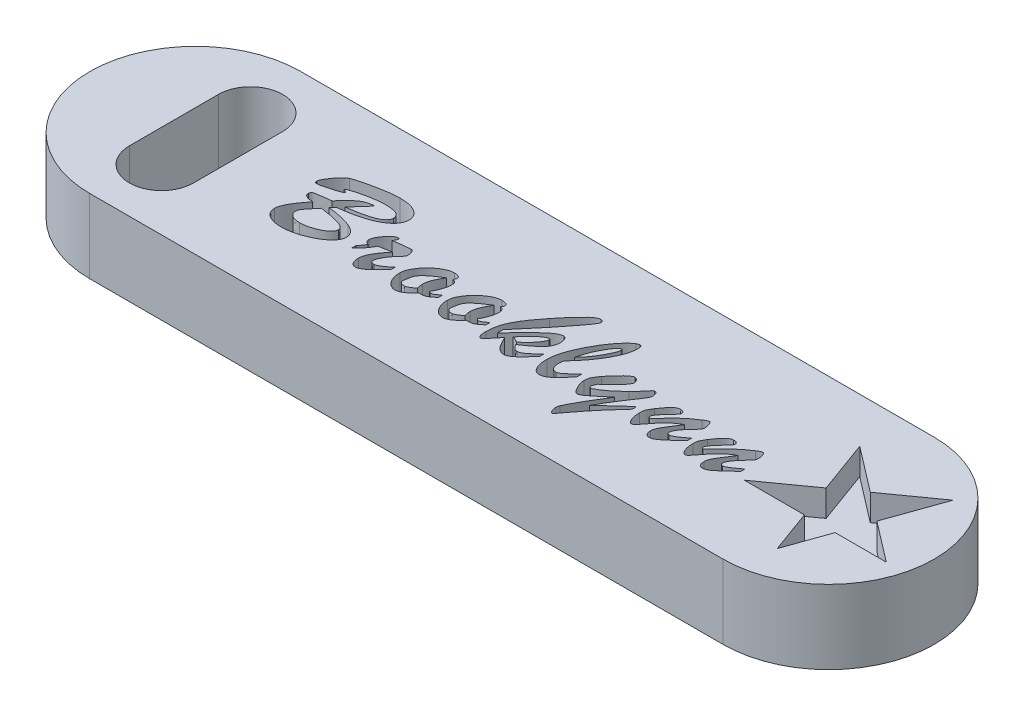
SolidWorks part; units mm, degrees
ref_plane "Front Plane" through (0, 0, 0) normal (0, 0, 1) x (1, 0, 0)
ref_plane "Top Plane" through (0, 0, 0) normal (0, 1, 0) x (1, 0, 0)
ref_plane "Right Plane" through (0, 0, 0) normal (1, 0, 0) x (0, 0, -1)
sketch "Sketch2" plane through (0, 0, 0) normal (0, 1, 0) x (1, 0, 0)
  line L0 (-42.129, 2.7124) -> (34.071, 2.7124) construction
  line L1 (-42.129, 15.4124) -> (34.071, 15.4124)
  line L2 (-42.129, -9.9876) -> (34.071, -9.9876)
  arc A0 (-42.129, 15.4124) -> (-42.129, -9.9876) centre (-42.129, 2.7124) ccw
  arc A1 (34.071, -9.9876) -> (34.071, 15.4124) centre (34.071, 2.7124) ccw
  point P2 (-4.029, 2.7124)
  dimension "D2" = 76.2
  dimension "D1" = 25.4
extrude "Boss-Extrude1" add sketch "Sketch2" along normal blind 8.89
sketch "Sketch5" plane through (0, 8.89, 0) normal (0, 1, 0) x (1, 0, 0)
  line L0 (-40.8401, 8.0714) -> (-40.8401, -2.6467) construction
  line L1 (-36.9745, 8.0714) -> (-36.9745, -2.6467)
  line L2 (-44.7056, 8.0714) -> (-44.7056, -2.6467)
  line L3 (34.071, 15.4124) -> (-42.129, 15.4124) construction
  arc A0 (-36.9745, 8.0714) -> (-44.7056, 8.0714) centre (-40.8401, 8.0714) ccw
  arc A1 (-44.7056, -2.6467) -> (-36.9745, -2.6467) centre (-40.8401, -2.6467) ccw
  point P2 (-40.8401, 2.7124)
  dimension "D1" = 12.7
extrude "Cut-Extrude1" cut sketch "Sketch5" against normal blind 38.1
sketch "Sketch6" plane through (0, 8.89, 0) normal (0, 1, 0) x (1, 0, 0)
  line L0 (41.7579, 9.9889) -> (39.3606, 3.2202)
  line L1 (36.2251, -5.633) -> (34.3494, -0.4882)
  line L2 (30.5296, 9.9889) -> (35.9501, 5.8342)
  line L3 (44.1988, -0.4882) -> (38.0472, -0.4882)
  line L4 (27.1123, -0.4882) -> (32.8523, 3.6181)
  line L5 (39.3606, 3.2202) -> (44.1988, -0.4882)
  line L6 (35.9501, 5.8342) -> (41.7579, 9.9889)
  line L7 (32.8523, 3.6181) -> (30.5296, 9.9889)
  line L8 (34.3494, -0.4882) -> (27.1123, -0.4882)
  line L9 (38.0472, -0.4882) -> (36.2251, -5.633)
  text T0 "Brooklynn" font "Brush Script MT" height in points 48
extrude "Cut-Extrude2" cut sketch "Sketch6" against normal blind 3.175
sketch "Sketch8" plane through (0, 0, 0) normal (0, -1, 0) x (-1, 0, 0)
  line L0 (33.3412, 10.4771) -> (30.9439, 3.7084)
  line L1 (27.8084, -5.1448) -> (25.9327, 0)
  line L2 (22.1129, 10.4771) -> (27.5334, 6.3224)
  line L3 (35.7821, 0) -> (29.6305, 0)
  line L4 (18.6956, 0) -> (24.4356, 4.1063)
  line L5 (30.9439, 3.7084) -> (35.7821, 0)
  line L6 (27.5334, 6.3224) -> (33.3412, 10.4771)
  line L7 (24.4356, 4.1063) -> (22.1129, 10.4771)
  line L8 (25.9327, 0) -> (18.6956, 0)
  line L9 (29.6305, 0) -> (27.8084, -5.1448)
  line L10 (6.9928, 10.4771) -> (4.5955, 3.7084)
  line L11 (1.46, -5.1448) -> (-0.4157, 0)
  line L12 (-4.2355, 10.4771) -> (1.1851, 6.3224)
  line L13 (9.4337, 0) -> (3.2821, 0)
  line L14 (-7.6527, 0) -> (-1.9128, 4.1063)
  line L15 (4.5955, 3.7084) -> (9.4337, 0)
  line L16 (1.1851, 6.3224) -> (6.9928, 10.4771)
  line L17 (-1.9128, 4.1063) -> (-4.2355, 10.4771)
  line L18 (-0.4157, 0) -> (-7.6527, 0)
  line L19 (3.2821, 0) -> (1.46, -5.1448)
  line L20 (-21.2628, 10.4771) -> (-23.66, 3.7084)
  line L21 (-26.7955, -5.1448) -> (-28.6712, 0)
  line L22 (-32.491, 10.4771) -> (-27.0705, 6.3224)
  line L23 (-18.8218, 0) -> (-24.9734, 0)
  line L24 (-35.9083, 0) -> (-30.1683, 4.1063)
  line L25 (-23.66, 3.7084) -> (-18.8218, 0)
  line L26 (-27.0705, 6.3224) -> (-21.2628, 10.4771)
  line L27 (-30.1683, 4.1063) -> (-32.491, 10.4771)
  line L28 (-28.6712, 0) -> (-35.9083, 0)
  line L29 (-24.9734, 0) -> (-26.7955, -5.1448)
extrude "Cut-Extrude3" cut sketch "Sketch8" against normal blind 3.175
